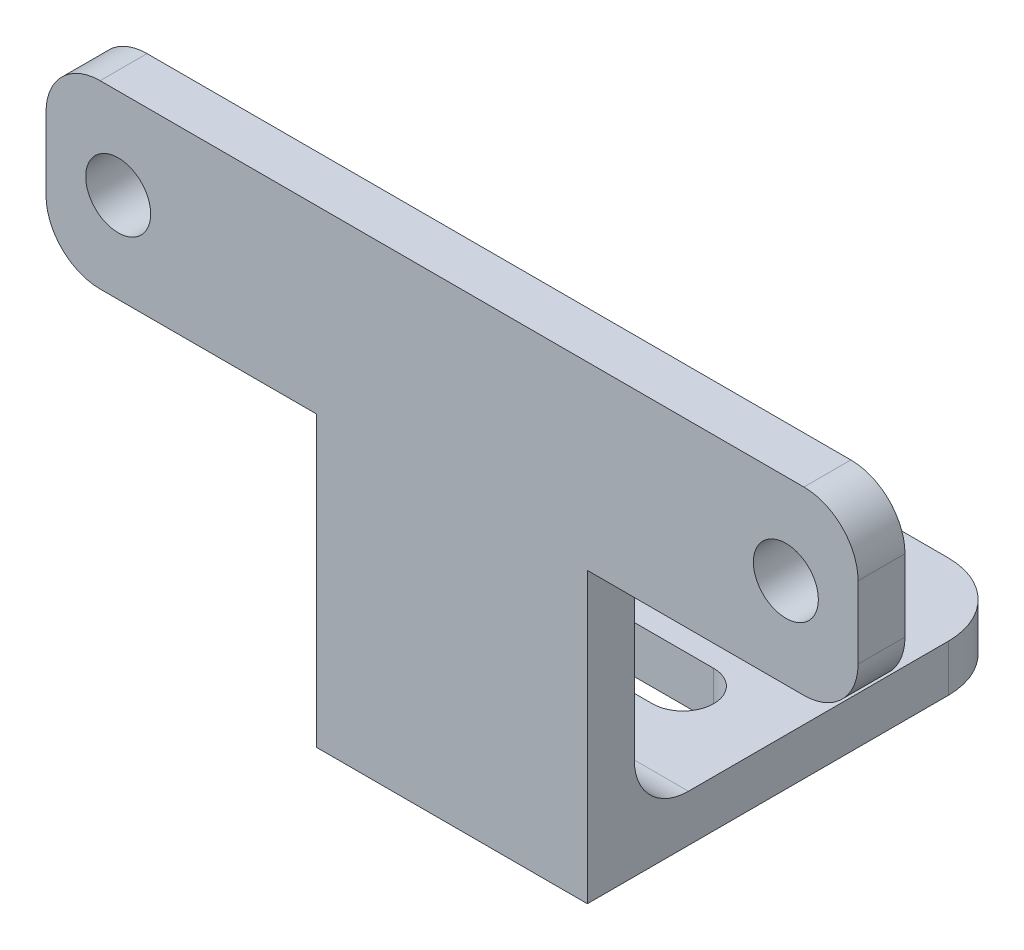
SolidWorks part; units mm, degrees
ref_plane "前视基准面" through (0, 0, 0) normal (0, 0, 1) x (1, 0, 0)
ref_plane "上视基准面" through (0, 0, 0) normal (0, 1, 0) x (1, 0, 0)
ref_plane "右视基准面" through (0, 0, 0) normal (1, 0, 0) x (0, 0, -1)
sketch "草图2" plane through (0, 0, 0) normal (0, 1, 0) x (1, 0, 0)
  line L1 (-7.5, 24) -> (7.5, 24)
  line L2 (-7.5, 24) -> (-7.5, 0)
  line L3 (-7.5, 0) -> (7.5, 0)
  line L4 (7.5, 24) -> (7.5, 0)
  dimension "D1" = 15
  dimension "D2" = 24
extrude "凸台-拉伸1" add sketch "草图2" along normal blind 2.6
sketch "草图4" plane through (0, 0, 0) normal (0, 0, 1) x (1, 0, 0)
  line L0 (7.5, 0) -> (-7.5, 0)
  line L1 (-7.5, 0) -> (-7.5, 11.6143)
  line L2 (-7.5, 11.6143) -> (-11.0095, 11.6143)
  line L3 (-11.0095, 11.6143) -> (-11.0095, 18.4819)
  line L4 (-11.0095, 18.4819) -> (11.0095, 18.4819)
  line L6 (0, 0) -> (0, 13.4818) construction
  line L7 (11.0095, 11.6143) -> (11.0095, 18.4819)
  line L8 (7.5, 11.6143) -> (11.0095, 11.6143)
  line L9 (7.5, 0) -> (7.5, 11.6143)
  point P14 (11.3289, 19.4727)
sketch "草图5" plane through (0, 0, 0) normal (0, 0, 1) x (1, 0, 0)
  line L0 (0, 0) -> (0, -25.4003) construction
  line L1 (-7.5, 0) -> (7.5, 0)
  line L2 (-7.5, 0) -> (-7.5, 16)
  line L3 (-7.5, 16) -> (7.5, 16)
  line L4 (7.5, 0) -> (7.5, 16)
  line L5 (-22.5, 16) -> (22.5, 16)
  line L6 (-22.5, 16) -> (-22.5, 26)
  line L7 (-22.5, 26) -> (22.5, 26)
  line L8 (22.5, 16) -> (22.5, 26)
  point P12 (19.9663, 20.6102)
  line M10 (7.5, 2.6) -> (-7.5, 2.6)
  dimension "D1" = 16
  dimension "D2" = 10
  dimension "D3" = 45
extrude "凸台-拉伸2" add sketch "草图5" against normal blind 2.6 contours L4 L3 L2 M10 | L5 L8 L7 L6 L3 region at (0, 9.3, 0) region at (0, 21, 0)
fillet "圆角1" radius 4 2 edges at (-7.5, 1.3, -24) (7.5, 1.3, -24)
hole_wizard "M3 间隙槽口3" positions "草图9" profile "草图10" hole size "M3" standard "GB"
sketch "草图9" plane through (0, 0, 0) normal (0, 0, 1) x (1, 0, 0)
  line L1 (0, 0) -> (0, -37.0636) construction
  line L2 (-22.5, 16) -> (-22.5, 26) construction
  line L3 (-22.5, 21) -> (-8.7585, 21) construction
  point P0 (-18.5, 21)
  point P4 (18.5, 21)
  dimension "D2" = 37
sketch "草图10" plane through (-18.5, 21, 0) normal (1, 0, 0) x (0, -1, 0)
  line L0 (0, 0) -> (0, 33.8315)
  line L1 (0, 33.8315) -> (1.8, 32.75)
  line L2 (1.8, 32.75) -> (1.8, 0)
  line L5 (1.8, 0) -> (0, 0)
  line L10 (0, 33.8315) -> (-1.8, 32.75) construction
  line L11 (0, -6.35) -> (0, 107.95) construction
  dimension "孔直径" = 3.6
  dimension "孔深度" = 32.75
  dimension "导头角度" = 118
fillet "圆角2" radius 3 4 edges at (-22.5, 26, -1.3) (-22.5, 16, -1.3) (22.5, 26, -1.3) (22.5, 16, -1.3)
fillet "圆角3" radius 3 1 edges at (0, 2.6, -2.6)
hole_wizard "M3 间隙槽口5" positions "草图11" profile "草图12" size "M3" standard "GB" slot yes
sketch "草图11" plane through (0, 2.6, 0) normal (0, 1, 0) x (1, 0, 0)
  line L0 (-4, 18.5) -> (4, 18.5) construction
  line L1 (3.5, 24) -> (-3.5, 24) construction
  point P0 (0, 18.5)
  point P4 (0, 10.5)
  dimension "D1" = 8
  dimension "D2" = 8
  dimension "5.5" = 5.5
sketch "草图12" plane through (0, 2.6, -18.5) normal (1, 0, 0) x (0, 0, 1)
  line L0 (0, 0) -> (0, 33.7715)
  line L1 (0, 33.7715) -> (1.7, 32.75)
  line L2 (1.7, 32.75) -> (1.7, 0)
  line L5 (1.7, 0) -> (0, 0)
  line L10 (0, 33.7715) -> (-1.7, 32.75) construction
  line L11 (0, -6.35) -> (0, 107.95) construction
  dimension "孔直径" = 3.4
  dimension "孔深度" = 32.75
  dimension "导头角度" = 118
